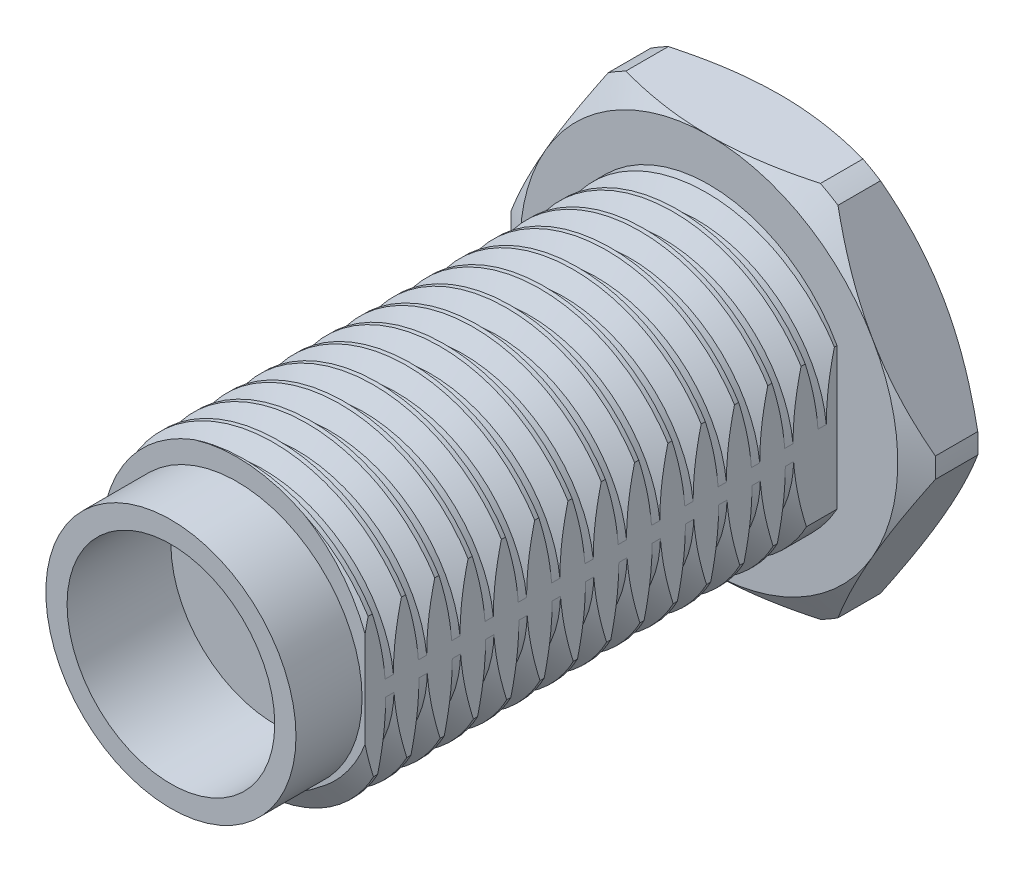
SolidWorks part; units mm, degrees
note: The reader was unsure of these and kept them because the rebuilt part matched: shared geometry of "Sketch1<3>", "Sketch1<4>", "Sketch1<5>", "Sketch1<6>".
material "Pure Gold"
ref_plane "Front" through (0, 0, 0) normal (0, 0, 1) x (1, 0, 0)
ref_plane "Top" through (0, 0, 0) normal (0, 1, 0) x (1, 0, 0)
ref_plane "Right" through (0, 0, 0) normal (1, 0, 0) x (0, 0, -1)
sketch "Sketch1" plane through (0, 0, 0) normal (0, 0, 1) x (1, 0, 0)
  line L0 (-12.5177, 0) -> (12.5177, 0) construction
  line L1 (-2.3094, 4) -> (-4.6188, 0)
  line L2 (-4.6188, 0) -> (-2.3094, -4)
  line L3 (-2.3094, -4) -> (2.3094, -4)
  line L4 (2.3094, -4) -> (4.6188, 0)
  line L5 (4.6188, 0) -> (2.3094, 4)
  line L6 (2.3094, 4) -> (-2.3094, 4)
  line L7 (0, -12.7875) -> (0, 12.7875) construction
  line L8 (2.7129, 1.5) -> (2.7129, -1.5)
  circle A0 centre (0, 0) radius 4 construction
  circle A1 centre (0, 0) radius 0.95
  arc A2 (2.7129, 1.5) -> (2.7129, -1.5) centre (0, 0) ccw
  circle A3 centre (0, 0) radius 2.2
  circle A4 centre (0, 0) radius 0.5
  circle A5 centre (0, 0) radius 0.6
  circle A6 centre (0, 0) radius 4.5
  circle A7 centre (0, 0) radius 0.25
  point P11 (0, 0)
  point P14 (0, 0)
  point P16 (2.7129, 0)
  point P25 (-3.1, 0)
  dimension "D2" = 1.9
  dimension "D3" = 1
  dimension "D4" = 4.4
  dimension "D6" = 1.2
  dimension "D5" = 3.1
  dimension "D7" = 9
  dimension "D8" = 0.5
  dimension "D9" = 3
  dimension "D1" = 8
extrude "Boss-Extrude1" add sketch "Sketch1" along normal blind 1.5
extrude "Boss-Extrude2" add sketch "Sketch1<3>" along normal blind 12.9
sketch "Sketch1<3>" plane through (0, 0, 0) normal (0, 0, 1) x (1, 0, 0) same geometry as "Sketch1"
extrude "Boss-Extrude3" add sketch "Sketch1<4>" along normal blind 10.7 contours A3 A1 | A1 A5
sketch "Sketch1<4>" plane through (0, 0, 0) normal (0, 0, 1) x (1, 0, 0) same geometry as "Sketch1"
extrude "Boss-Extrude4" add sketch "Sketch1<5>" against normal blind 1.1 contours A7 | A5 A4
sketch "Sketch1<5>" plane through (0, 0, 0) normal (0, 0, 1) x (1, 0, 0) same geometry as "Sketch1"
sketch "Sketch2" plane through (0, 0, 12.9) normal (0, 0, 1) x (1, 0, 0)
  circle A0 centre (0, 0) radius 2.65
  circle A1 centre (0, 0) radius 3.5
  dimension "D1" = 5.3
  dimension "D2" = 7
extrude "Cut-Extrude1" cut sketch "Sketch2" against normal blind 1.4
thread "Thread1" pitch 0.7056 start angle 0, offset 0, length 0, pitch 0.7056, diameter 6.2
ref_plane "Plane2" through (3.1, 0, 1.5) normal (0, -1, 0) x (1, 0, 0)
sketch "Thread Profile2" plane through (3.1, 0, 1.5) normal (0, -1, 0) x (1, 0, 0)
  line L0 (0, 0) -> (0, 0.7056) construction
  line L11 (0, 0) -> (0, 0.6174)
  line L12 (0, 0.6174) -> (-0.3819, 0.3969)
  line L13 (-0.3819, 0.3969) -> (-0.3819, 0.2205)
  line L15 (-0.3819, 0.2205) -> (0, 0)
  line L17 (-0.3819, 0.3087) -> (0, 0.3087) construction
  point P2 (0, 0)
  dimension "Pitch" = 0.7056
  dimension "Profile_Angle" = 60
  dimension "Profile_Land" = 0.1764
  dimension "Profile_Height" = 0.3819
extrude "Boss-Extrude5" add sketch "Sketch1<6>" along normal blind 10.7 separate body contours A5 A4
sketch "Sketch1<6>" plane through (0, 0, 0) normal (0, 0, 1) x (1, 0, 0) same geometry as "Sketch1"
sketch "Sketch9" plane through (0, 0, 0) normal (0, 0, 1) x (1, 0, 0)
  circle A0 centre (0, 0) radius 4
  dimension "D1" = 8
sketch "Sketch10" plane through (0, 0, 0) normal (0, 1, 0) x (1, 0, 0)
  line L0 (0, 1.8823) -> (0, -14.0692) construction
  line L1 (-4, 0) -> (-4.5, 0)
  line L2 (-4, 0) -> (-4.5, -0.3)
  line L4 (-4.5, 0) -> (-4.5, -0.3)
  line L5 (0.6, 1.1) -> (-0.6, 1.1) construction
  line L6 (-4, -0.75) -> (-5.1444, -0.75) construction
  line L7 (-2.4333, -1.5) -> (-4.4949, -1.5) construction
  line L8 (-4, -1.5) -> (-4.5, -1.5)
  line L9 (-4, 0) -> (-4, -1.5) construction
  line L10 (-4.5, -1.5) -> (-4.5, -1.2)
  line L11 (-4, -1.5) -> (-4.5, -1.2)
  line L12 (-0.25, 0.88) -> (-0.25, 1.1)
  line L14 (0.25, 1.1) -> (-0.25, 1.1) construction
  line L15 (-0.25, 1.1) -> (0, 1.1)
  arc A0 (-0.03, 1.1) -> (-0.25, 0.88) centre (-0.03, 0.88) ccw
  dimension "D4" = 0.25
  dimension "D5" = 0.22
  dimension "D1" = 0.5
  dimension "D2" = 0.3
  dimension "D3" = 4
  dimension "D6" = 0.75
  dimension "D7" = 0.22
  dimension "D8" = 0.22
revolve "Cut-Revolve1" cut sketch "Sketch10" angle 360 about L0
